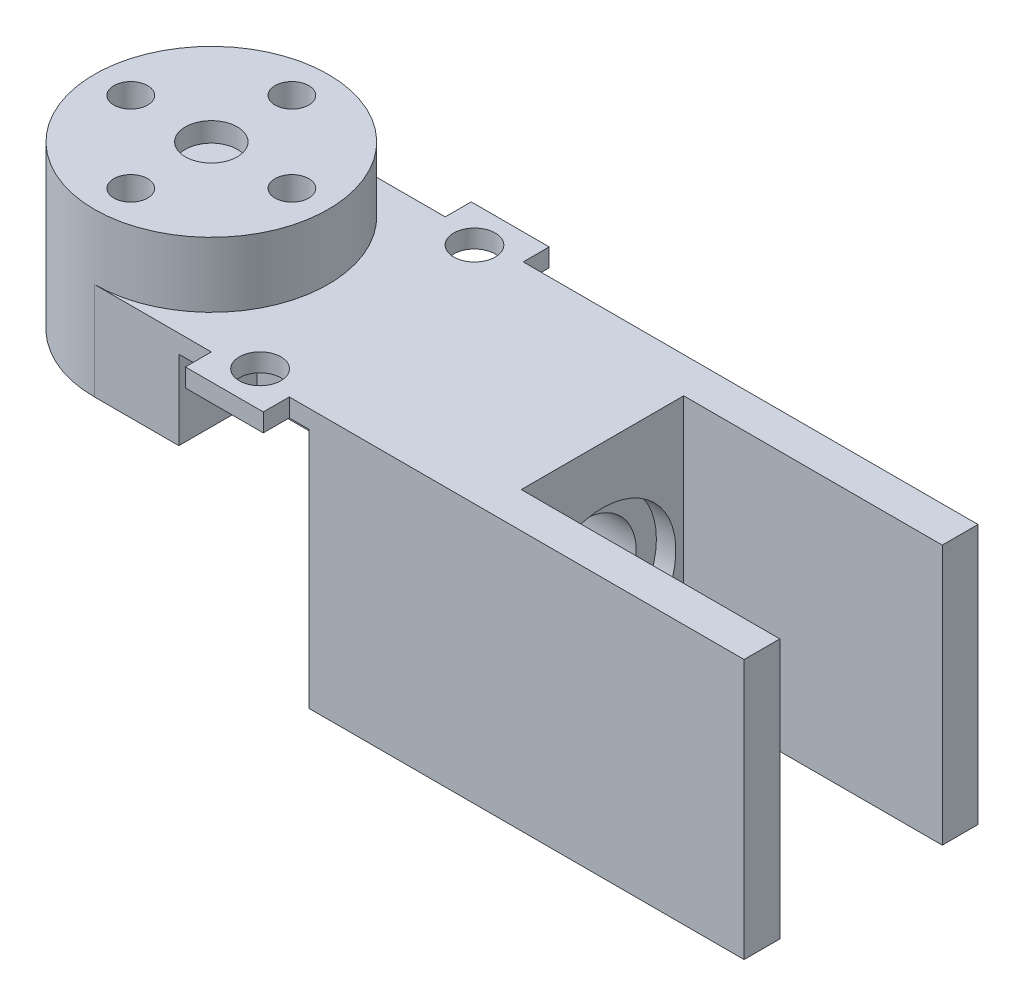
SolidWorks part; units mm, degrees
ref_plane "Front Plane" through (0, 0, 0) normal (0, 0, 1) x (1, 0, 0)
ref_plane "Top Plane" through (0, 0, 0) normal (0, 1, 0) x (1, 0, 0)
ref_plane "Right Plane" through (0, 0, 0) normal (1, 0, 0) x (0, 0, -1)
sketch "Sketch1" plane through (0, 0, 0) normal (0, 1, 0) x (1, 0, 0)
  circle A0 centre (0, 0) radius 9
  dimension "D1" = 18
extrude "Boss-Extrude1" add sketch "Sketch1" along normal blind 25
sketch "Sketch2" plane through (0, 0, 0) normal (0, -1, 0) x (1, 0, 0)
  line L2 (0, 0) -> (0, 6.2) construction
  circle A0 centre (0, 6.2) radius 2.4
  circle A1 centre (6.2, 0) radius 2.4
  circle A2 centre (0, -6.2) radius 2.4
  circle A3 centre (-6.2, 0) radius 2.4
  point P13 (0, 0)
  dimension "D8" = 4.8
  dimension "D1" = 4
  dimension "D2" = 6.2
extrude "Cut-Extrude1" cut sketch "Sketch2" against normal offset from surface (22 mm away) 3 up to face at (0, 25, 9)
sketch "Sketch4" plane through (0, 0, 0) normal (0, -1, 0) x (1, 0, 0)
  line L1 (0, 0) -> (0, 6.2) construction
  circle A0 centre (0, 6.2) radius 1.3
  circle A1 centre (6.2, 0) radius 1.3
  circle A2 centre (0, -6.2) radius 1.3
  circle A3 centre (-6.2, 0) radius 1.3
  point P15 (0, 0)
  dimension "D4" = 2.6
  dimension "D1" = 4
  dimension "D2" = 6.2
extrude "Cut-Extrude2" cut sketch "Sketch4" against normal through all
sketch "Sketch19" plane through (0, 25, 0) normal (0, 1, 0) x (1, 0, 0)
  circle A0 centre (0, 0) radius 2
  dimension "D1" = 4
extrude "Cut-Extrude10" cut sketch "Sketch19" against normal blind 1.5
sketch "Sketch6" plane through (0, 0, 0) normal (0, 1, 0) x (1, 0, 0)
  line L0 (0, 0) -> (0, 5.05) construction
  line L1 (0, 0) -> (0, -5.05) construction
  line L2 (0, 9) -> (0, 5.05) construction
  line L3 (0, -5.05) -> (0, -9) construction
  line L4 (30.1, 6.25) -> (50, 6.25)
  line L5 (30.1, -6.25) -> (50, -6.25)
  line L6 (0, 9) -> (50, 9)
  line L7 (0, -9) -> (50, -9)
  line L8 (50, -9) -> (50, -6.25)
  line L9 (50, 9) -> (50, 6.25)
  line L10 (30.1, 6.25) -> (30.1, -6.25)
  arc A0 (0, -9) -> (0, 9) centre (0, 0) ccw
  point P6 (50, 7.625)
  point P14 (9, 0)
  point P15 (30.1, 0)
  dimension "D1" = 18
  dimension "D7" = 2.75
  dimension "D2" = 5.05
  dimension "D3" = 5.05
  dimension "D4" = 50
  dimension "D5" = 50
  dimension "D6" = 21.1
  dimension "D8" = 2.75
extrude "Boss-Extrude2" add sketch "Sketch6" along normal blind 20
sketch "Sketch8" plane through (30.1, 0, 0) normal (1, 0, 0) x (0, 0, -1)
  line L0 (0, 0) -> (0, 10) construction
  circle A0 centre (0, 10) radius 5.65
  dimension "D2" = 11.3
  dimension "D1" = 10
extrude "Cut-Extrude3" cut sketch "Sketch8" against normal blind 1.5 and the other way through all contours A0
sketch "Sketch10" plane through (0, 0, 0) normal (0, -1, 0) x (1, 0, 0)
  line L0 (9, 0) -> (9, 9)
  line L1 (0, 9) -> (50, 9) construction
  line L2 (9, 9) -> (0, 9)
  line L3 (0, -9) -> (9, -9)
  line L4 (50, -9) -> (0, -9) construction
  line L5 (9, -9) -> (9, 0)
  arc A0 (0, 9) -> (0, -9) centre (0, 0) ccw
extrude "Cut-Extrude5" cut sketch "Sketch10" against normal blind 12.5
fillet "Fillet1" radius 5 1 edges at (9, 0, 0)
sketch "Sketch11" plane through (28.6, 0, 0) normal (1, 0, 0) x (0, 0, -1)
  line L0 (0, 0) -> (0, 10) construction
  circle A0 centre (0, 10) radius 4.1
  dimension "D2" = 8.2
  dimension "D1" = 10
extrude "Cut-Extrude6" cut sketch "Sketch11" against normal blind 7
fillet "Fillet4" radius 0.5 1 edges at (9, 12.5, 0)
sketch "Sketch12" plane through (0, 0, 9) normal (0, 0, 1) x (1, 0, 0)
  line L0 (9, 5) -> (9, 20) construction
  line L2 (9, 20) -> (15, 20)
  line L3 (9, 20) -> (9, 18.6)
  line L4 (9, 18.6) -> (15, 18.6)
  line L5 (15, 20) -> (15, 18.6)
  dimension "D1" = 6
  dimension "D2" = 1.4
extrude "Boss-Extrude3" add sketch "Sketch12" along normal blind 2 and the other way blind 20
sketch "Sketch13" plane through (0, 20, 0) normal (0, 1, 0) x (1, 0, 0)
  line L0 (9, 0) -> (12, 0) construction
  line L2 (9, 9) -> (9, -9) construction
  line L3 (12, 0) -> (12, 8.25) construction
  circle A2 centre (12, 8.25) radius 1.6
  circle A3 centre (12, -8.25) radius 1.6
  dimension "D2" = 8.25
  dimension "D3" = 3.2
  dimension "D1" = 3
extrude "Cut-Extrude7" cut sketch "Sketch13" against normal through all
sketch "Sketch14" plane through (0, 0, 9) normal (0, 0, 1) x (1, 0, 0)
  line L0 (9, 20) -> (9, 12) construction
  line L5 (14, 0) -> (50, 0) construction
  line L6 (9, 18.6) -> (6.5, 18.6) construction
  line L7 (6.5, 18.6) -> (16.5, 18.6)
  line L8 (6.5, 18.6) -> (6.5, 0)
  line L9 (6.5, 0) -> (16.5, 0)
  line L10 (16.5, 18.6) -> (16.5, 0)
  dimension "D1" = 10
  dimension "D2" = 2.5
extrude "Cut-Extrude8" cut sketch "Sketch14" against normal blind 6
sketch "Sketch15" plane through (0, 0, -9) normal (0, 0, -1) x (-1, 0, 0)
  line L0 (-9, 18.6) -> (-6.5, 18.6) construction
  line L5 (-50, 0) -> (-14, 0) construction
  line L6 (-6.5, 18.6) -> (-16.5, 18.6)
  line L7 (-6.5, 18.6) -> (-6.5, 0)
  line L8 (-6.5, 0) -> (-16.5, 0)
  line L9 (-16.5, 18.6) -> (-16.5, 0)
  dimension "D1" = 2.5
  dimension "D2" = 10
extrude "Cut-Extrude9" cut sketch "Sketch15" against normal blind 6
sketch "Sketch20" plane through (0, 0, -3) normal (0, 0, -1) x (-1, 0, 0)
  line L0 (-6.5, 12.5) -> (-16.5, 12.5)
  line L1 (-16.5, 18.6) -> (-16.5, 0) construction
  line L2 (-16.5, 12.5) -> (-16.5, 0)
  line L3 (-16.5, 0) -> (-6.5, 0)
  line L4 (-6.5, 0) -> (-6.5, 12.5)
extrude "Cut-Extrude11" cut sketch "Sketch20" against normal up to next
